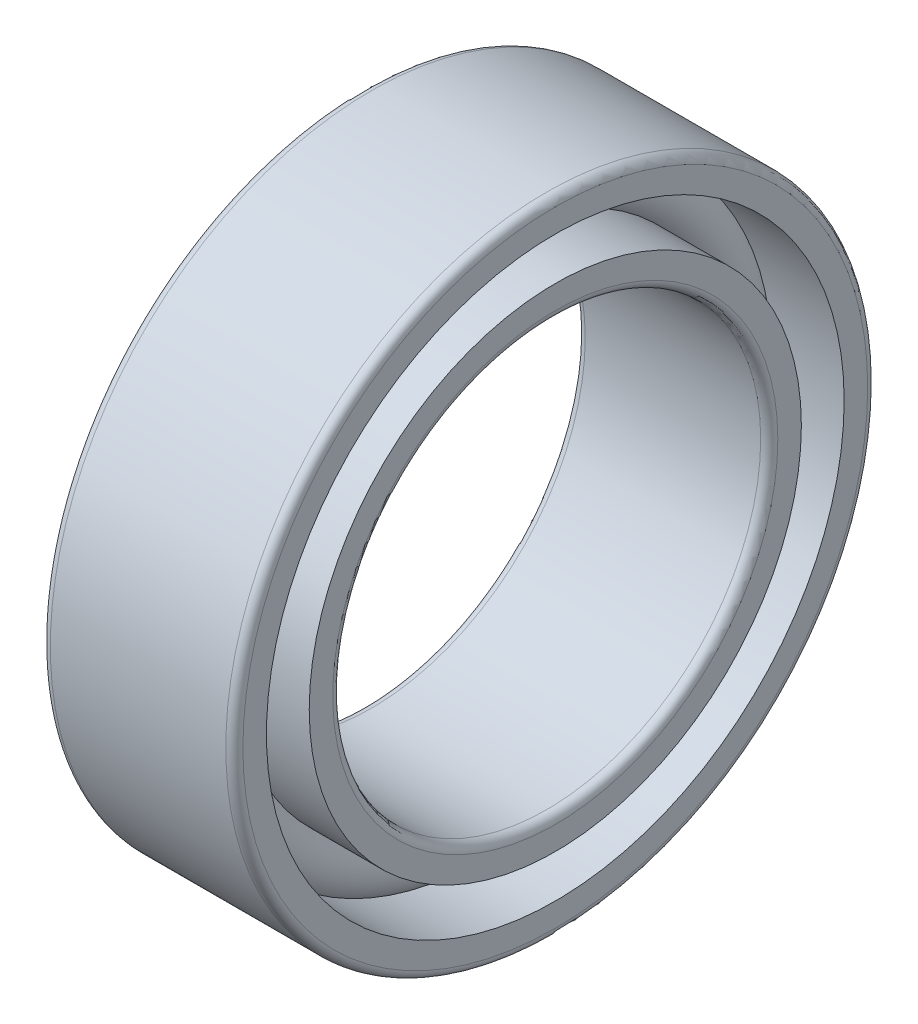
SolidWorks part; units mm, degrees
ref_plane "Plane1" through (0, 0, 0) normal (0, 0, 1) x (1, 0, 0)
ref_plane "Plane2" through (0, 0, 0) normal (0, 1, 0) x (1, 0, 0)
ref_plane "Plane3" through (0, 0, 0) normal (1, 0, 0) x (0, 0, -1)
sketch "Clipboard" plane through (0, 0, 0) normal (0, 0, 1) x (1, 0, 0)
  line L0 (-10, 0) -> (10, 0) construction
  line L1 (0, 0) -> (22.3471, -0.7804)
  line L2 (0, 0) -> (6.2462, 0.2181)
  line L3 (0, 0) -> (22.3471, -0.7804)
  line L4 (0, 0) -> (-22.3573, -0.3902)
  dimension "BallCLRad" = 6.25
sketch "CagSpiSke" plane through (0, 0, 0) normal (0, 0, 1) x (1, 0, 0)
  line L0 (0.075, 6.125) -> (0.075, 6.375)
  line L1 (0.075, 6.375) -> (-0.075, 6.375)
  line L2 (-0.075, 6.375) -> (-0.075, 6.125)
  line L3 (-0.075, 6.125) -> (0.075, 6.125)
  line L4 (-20.6375, 0) -> (20.6375, 0) construction
  line L5 (0, 0) -> (0, 23.7692) construction
  dimension "OD" = 12.75
  dimension "ID" = 12.25
revolve "CageSpine" add sketch "CagSpiSke" angle 0.001 about L4 reverse direction yes
ref_axis "Axis1" through (-50, 0, 0) along (1, 0, 0)
sketch "CagBalSke" plane through (0, 0, 0) normal (0, 0, 1) x (1, 0, 0)
  line L0 (-0.825, 6.25) -> (0.825, 6.25)
  line L1 (-1.905, 6.25) -> (1.905, 6.25) construction
  line L2 (-10, 0) -> (10, 0) construction
  line L3 (0, 0) -> (0, 24) construction
  arc A0 (0.825, 6.25) -> (-0.825, 6.25) centre (0, 6.25) cw
  dimension "BallCLRad" = 6.25
revolve "CageBall" [suppressed] add sketch "CagBalSke" angle 360 about L1 reverse direction yes
pattern_circular "CageBalls" [suppressed] count 2 every 180 about axis through (-50, 0, 0) along (1, 0, 0)
sketch "CagTrmODSke" plane through (0, 0, 0) normal (0, 0, 1) x (1, 0, 0)
  line L0 (0.826, 6.375) -> (0.826, 7.076)
  line L1 (0.826, 7.076) -> (-0.826, 7.076)
  line L2 (-0.826, 7.076) -> (-0.826, 6.375)
  line L3 (-0.826, 6.375) -> (0.826, 6.375)
  line L4 (-20.6375, 0) -> (20.6375, 0) construction
  line L5 (0, 0) -> (0, 25) construction
  dimension "Width" = 1.652
  dimension "ID" = 12.75
  dimension "OD" = 14.152
revolve "CageTrimOD" [suppressed] cut sketch "CagTrmODSke" angle 360 about L4 reverse direction yes
sketch "CagTrmIDSke" plane through (0, 0, 0) normal (0, 0, 1) x (1, 0, 0)
  line L0 (0.826, 5.426) -> (0.826, 6.125)
  line L1 (0.826, 6.125) -> (-0.826, 6.125)
  line L2 (-0.826, 6.125) -> (-0.826, 5.426)
  line L3 (-0.826, 5.426) -> (0.826, 5.426)
  line L4 (-20.6375, 0) -> (20.6375, 0) construction
  line L5 (0, 0) -> (0, 25) construction
  dimension "Width" = 1.652
  dimension "ID" = 10.852
  dimension "OD" = 12.25
revolve "CageTrimID" [suppressed] cut sketch "CagTrmIDSke" angle 360 about L4 reverse direction yes
sketch "BalSimSke" plane through (0, 0, 0) normal (0, 0, 1) x (1, 0, 0)
  line L0 (-10, 0) -> (10, 0) construction
  line L1 (-10, 6.25) -> (10, 6.25) construction
  line L2 (0, 0) -> (0, 23) construction
  circle A0 centre (0, 6.25) radius 0.75
  dimension "BallCLRad" = 6.25
  dimension "Ball_diameter" = 1.5
revolve "BallsSimplified" add sketch "BalSimSke" angle 360 about L0
sketch "BalDetSke" plane through (0, 0, 0) normal (0, 0, 1) x (1, 0, 0)
  line L0 (-0.75, 6.25) -> (0.75, 6.25)
  line L1 (-1.905, 6.25) -> (1.905, 6.25) construction
  line L2 (0, 0) -> (0, 25) construction
  arc A0 (0.75, 6.25) -> (-0.75, 6.25) centre (0, 6.25) cw
  dimension "BallCLRad" = 6.25
  dimension "Ball_diameter" = 1.5
revolve "BallDetailed" [suppressed] add sketch "BalDetSke" angle 360 about L1 reverse direction yes
sketch "InnRacSke" plane through (0, 0, 0) normal (0, 0, 1) x (1, 0, 0)
  line L0 (-0.525, 5.75) -> (-2.25, 5.75)
  line L1 (-2.25, 5.75) -> (-2.25, 5.2)
  line L2 (-2.05, 5) -> (2.05, 5)
  line L3 (2.25, 5.2) -> (2.25, 5.75)
  line L4 (2.25, 5.75) -> (0.525, 5.75)
  line L5 (-20.6375, 0) -> (20.6375, 0) construction
  line L6 (0, 0) -> (0, 30) construction
  arc A0 (-2.25, 5.2) -> (-2.05, 5) centre (-2.05, 5.2) ccw
  arc A1 (2.05, 5) -> (2.25, 5.2) centre (2.05, 5.2) ccw
  arc A2 (0.525, 5.75) -> (-0.525, 5.75) centre (0, 6.25) cw
  dimension "BallCLRad" = 6.25
  dimension "Fillet_radius" = 0.2
  dimension "Ball_diameter" = 1.45
  dimension "ID" = 10
  dimension "OD" = 11.5
  dimension "Width" = 4.5
revolve "InnerRace" add sketch "InnRacSke" angle 360 about L5 reverse direction yes
sketch "OutRacSke" plane through (0, 0, 0) normal (0, 0, 1) x (1, 0, 0)
  line L0 (-0.525, 6.75) -> (-2.25, 6.75)
  line L1 (-2.25, 6.75) -> (-2.25, 7.3)
  line L2 (-2.05, 7.5) -> (2.05, 7.5)
  line L3 (2.25, 7.3) -> (2.25, 6.75)
  line L4 (2.25, 6.75) -> (0.525, 6.75)
  line L5 (-20.6375, 0) -> (20.6375, 0) construction
  line L6 (0, 0) -> (0, 30) construction
  arc A0 (-2.25, 7.3) -> (-2.05, 7.5) centre (-2.05, 7.3) cw
  arc A1 (2.05, 7.5) -> (2.25, 7.3) centre (2.05, 7.3) cw
  arc A2 (0.525, 6.75) -> (-0.525, 6.75) centre (0, 6.25) ccw
  dimension "BallCLRad" = 6.25
  dimension "Fillet_radius" = 0.2
  dimension "Ball_diameter" = 1.45
  dimension "Width" = 4.5
revolve "OuterRace" add sketch "OutRacSke" angle 360 about L5 reverse direction yes
pattern_circular "BallsDetailed" [suppressed] count 2 every 180 about axis through (-50, 0, 0) along (1, 0, 0)
equation "\"BallCLRad@Clipboard\" = ( \"OD@OutRacSke\" + \"ID@InnRacSke\" ) / 4"
equation "\"BallCLRad@BalSimSke\" = \"BallCLRad@Clipboard\""
equation "\"BallCLRad@BalDetSke\" = \"BallCLRad@Clipboard\""
equation "\"BallCLRad@InnRacSke\" = \"BallCLRad@Clipboard\""
equation "\"BallCLRad@OutRacSke\" = \"BallCLRad@Clipboard\""
equation "\"Ball_diameter@InnRacSke\" = \"Ball_diameter@BalDetSke\" - 0.05"
equation "\"Ball_diameter@OutRacSke\" = \"Ball_diameter@BalDetSke\" - 0.05"
equation "\"Ball_diameter@BalSimSke\" = \"Ball_diameter@BalDetSke\""
equation "\"Width@OutRacSke\" = \"Width@InnRacSke\""
equation "\"Fillet_radius@OutRacSke\" = \"Fillet_radius@InnRacSke\""
equation "\"Max_count@Clipboard\" = int( 3.14159265 / atn(( \"Ball_diameter@BalDetSke\" / 2) / sqr( \"BallCLRad@Clipboard\"  *  \"BallCLRad@Clipboard\" - ( \"Ball_diameter@BalDetSke\" / 2) *  ( \"Ball_diameter@BalDetSke\" / 2))))"
equation "\"Max_count@Clipboard\" = ((sgn( \"Max_count@Clipboard\" - \"Count@Clipboard\" )-1)*( \"Max_count@Clipboard\" - \"Count@Clipboard\" ))/-2+ \"Count@Clipboard\""
equation "\"Count@BallsDetailed\" = int( \"Show_count@Clipboard\" ) "
equation "\"Count@BallsDetailed\" = ((sgn( \"Count@BallsDetailed\" - \"Max_count@Clipboard\" )-1)*( \"Count@BallsDetailed\" - \"Max_count@Clipboard\" ))/-2+ \"Max_count@Clipboard\""
equation "\"Count@BallsDetailed\" = ((sgn( \"Count@BallsDetailed\" - \"Min_count@Clipboard\" )+1)*( \"Count@BallsDetailed\" - \"Min_count@Clipboard\"))/2 +\"Min_count@Clipboard\""
equation "\"Angle@BallsDetailed\" = 360.0 / \"Max_count@Clipboard\""
equation "\"BallCLRad@CagBalSke\" = \"BallCLRad@Clipboard\""
equation "\"Count@CageBalls\" = \"Count@BallsDetailed\""
equation "\"Angle@CageBalls\" = \"Angle@BallsDetailed\""
equation "\"Angle@CageSpine\" =  \"Angle@CageBalls\" * ( \"Count@CageBalls\" -1 + int( \"Count@CageBalls\" / \"Max_count@Clipboard\" ) )  + 0.001 -  int( \"Count@CageBalls\" / \"Max_count@Clipboard\" ) * 0.001"
equation "\"Angle@CageSpine\" =  \"Angle@CageSpine\" * int( \"Min_count@Clipboard\" / 2) + int(1 / \"Min_count@Clipboard\")  * 0.001"
equation "\"CageWallOD@CagBalSke\" =  \"Ball_diameter@BalDetSke\" * 1.1"
equation "\"Thickness@CagSpiSke\" =  \"Ball_diameter@BalDetSke\" * 0.1"
equation "\"OD@CagTrmODSke\" = \"BallCLRad@Clipboard\" * 2 + \"CageWallOD@CagBalSke\" + 0.002"
equation "\"ID@CagTrmODSke\" = \"BallCLRad@Clipboard\" * 2 + \"Ball_diameter@BalDetSke\" / 6"
equation "\"OD@CagTrmIDSke\" = \"BallCLRad@Clipboard\" * 2 - \"Ball_diameter@BalDetSke\" / 6"
equation "\"ID@CagTrmIDSke\" = \"BallCLRad@Clipboard\" * 2 - \"CageWallOD@CagBalSke\" + 0.002"
equation "\"OD@CagSpiSke\" = \"ID@CagTrmODSke\""
equation "\"ID@CagSpiSke\" = \"OD@CagTrmIDSke\""
equation "\"Width@CagTrmODSke\" = \"CageWallOD@CagBalSke\" + 0.002"
equation "\"Width@CagTrmIDSke\" = \"CageWallOD@CagBalSke\" + 0.002"
